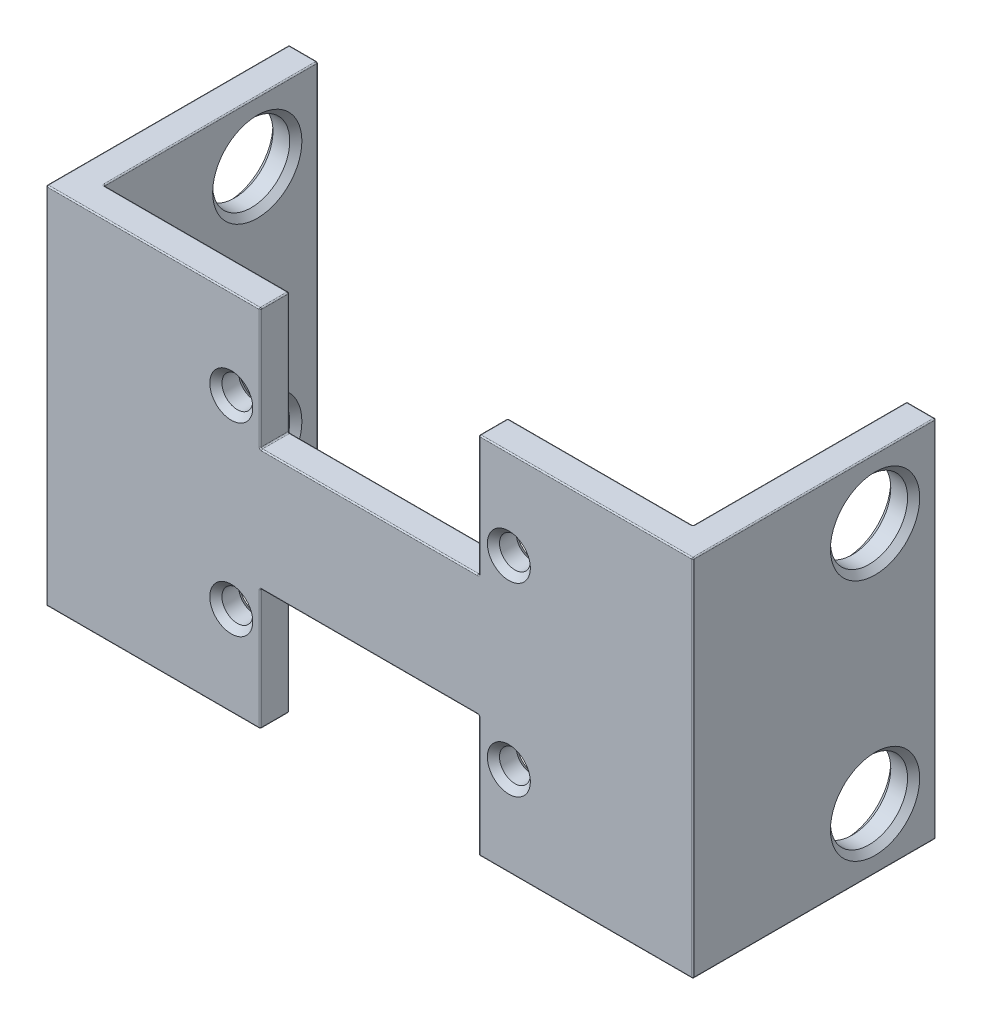
SolidWorks part; units mm, degrees
ref_plane "Front Plane" through (0, 0, 0) normal (0, 0, 1) x (1, 0, 0)
ref_plane "Top Plane" through (0, 0, 0) normal (0, 1, 0) x (1, 0, 0)
ref_plane "Right Plane" through (0, 0, 0) normal (1, 0, 0) x (0, 0, -1)
sketch "Sketch1" plane through (0, 0, 0) normal (0, 1, 0) x (1, 0, 0)
  line L0 (0, 0) -> (0, 17.6188)
  line L1 (0, 17.6188) -> (2.3813, 17.6188)
  line L2 (2.3813, 17.6188) -> (2.3813, -2.3812)
  line L3 (2.3813, -2.3812) -> (-50.8812, -2.3813)
  line L5 (-48.5, 0) -> (0, 0)
  line L6 (-48.5, 0) -> (-48.5, 17.6188)
  line L7 (-48.5, 17.6188) -> (-50.8812, 17.6188)
  line L8 (-50.8812, 17.6188) -> (-50.8812, -2.3813)
  dimension "D1" = 2.3813
  dimension "D2" = 20
  dimension "D4" = 2.3813
  dimension "D5" = 20
  dimension "D6" = 48.5
  dimension "D7" = 2.3813
extrude "Boss-Extrude1" add sketch "Sketch1" along normal blind 30
sketch "Sketch2" plane through (0, 0, 2.3812) normal (0, 0, 1) x (1, 0, 0)
  line L4 (-50.8812, 0) -> (2.3813, 0)
  line L5 (2.3813, 0) -> (2.3813, 30)
  line L6 (2.3813, 30) -> (-50.8812, 30)
  line L7 (-50.8812, 30) -> (-50.8812, 0)
  line L8 (-50.8812, 0) -> (2.3813, 0) construction
  line L9 (2.3813, 0) -> (2.3813, 30) construction
  line L10 (2.3813, 30) -> (-50.8812, 30) construction
  line L12 (-50.8812, 30) -> (-50.8812, 0) construction
  circle A0 centre (-35.64, 7.38) radius 1.27 construction
  circle A1 centre (-35.64, 7.38) radius 1.27
  circle A2 centre (-12.78, 7.38) radius 1.27 construction
  circle A3 centre (-12.78, 7.38) radius 1.27
  circle A4 centre (-12.78, 22.62) radius 1.27 construction
  circle A5 centre (-12.78, 22.62) radius 1.27
  circle A6 centre (-35.64, 22.62) radius 1.27 construction
  circle A7 centre (-35.64, 22.62) radius 1.27
  dimension "D1" = 0
extrude "Cut-Extrude1" cut sketch "Sketch2" against normal through all
sketch "Sketch3" plane through (2.3813, 0, 0) normal (1, 0, 0) x (0, 0, -1)
  line L4 (-2.3812, 0) -> (17.6188, 0)
  line L5 (17.6188, 0) -> (17.6188, 30)
  line L6 (17.6188, 30) -> (-2.3812, 30)
  line L7 (-2.3812, 30) -> (-2.3812, 0)
  line L8 (-2.3812, 0) -> (17.6188, 0) construction
  line L9 (17.6188, 0) -> (17.6188, 30) construction
  line L10 (17.6188, 30) -> (-2.3812, 30) construction
  line L11 (-2.3812, 30) -> (-2.3812, 0) construction
  circle A0 centre (12.6188, 25) radius 3.175
  circle A1 centre (12.6188, 5) radius 3.175
  point P2 (12.6188, 25)
  point P4 (12.6188, 5)
  dimension "D5" = 6.35
  dimension "D2" = 20
  dimension "D3" = 5
  dimension "D4" = 15
  dimension "D1" = 0
extrude "Cut-Extrude2" cut sketch "Sketch3" against normal through all
fillet "Fillet1" radius 0.1 24 edges at (-48.5, 15, -17.6188) (-50.8812, 15, -17.6188) (2.3813, 15, -17.6188) (0, 15, -17.6188) (-48.5, 0, -8.8094) (-49.6906, 0, -17.6188) (-50.8812, 0, -7.6188) (-24.25, 0, 2.3813) (2.3813, 0, -7.6188) (1.1906, 0, -17.6188) (0, 0, -8.8094) (-24.25, 0, 0) (0, 30, -8.8094) (1.1906, 30, -17.6188) (2.3813, 30, -7.6188) (-24.25, 30, 2.3813) (-50.8812, 30, -7.6188) (-49.6906, 30, -17.6188) (-48.5, 30, -8.8094) (-24.25, 30, 0) (-50.8812, 15, 2.3813) (2.3813, 15, 2.3812) (0, 15, 0) (-48.5, 15, 0)
chamfer "Chamfer1" distance 0.5 angle 45 16 edges at (0, 5, -15.7938) (2.3813, 5, -15.7938) (0, 25, -15.7938) (2.3813, 25, -15.7938) (-48.5, 25, -9.4437) (-50.8812, 25, -15.7938) (-48.5, 5, -9.4437) (-50.8812, 5, -15.7938) (-11.51, 7.38, 0) (-11.51, 7.38, 2.3812) (-11.51, 22.62, 0) (-11.51, 22.62, 2.3812) (-34.37, 7.38, 0) (-34.37, 7.38, 2.3812) (-34.37, 22.62, 0) (-34.37, 22.62, 2.3812)
sketch "Sketch4" plane through (0, 0, 2.3812) normal (0, 0, 1) x (1, 0, 0)
  line L0 (-50.7812, 15) -> (-44.8703, 15) construction
  line L4 (2.2813, 29.9) -> (-50.7812, 29.9)
  line L5 (-50.7812, 29.9) -> (-50.7812, 0.1)
  line L6 (-50.7812, 0.1) -> (2.2813, 0.1)
  line L7 (2.2813, 0.1) -> (2.2813, 29.9)
  line L8 (2.2813, 29.9) -> (-50.7812, 29.9) construction
  line L9 (-50.7812, 29.9) -> (-50.7812, 0.1) construction
  line L10 (-50.7812, 0.1) -> (2.2813, 0.1) construction
  line L11 (2.2813, 0.1) -> (2.2813, 29.9) construction
  line L17 (2.2813, 0) -> (-50.7812, 0) construction
  line L18 (2.2813, 0) -> (-50.7812, 0) construction
  line L19 (2.2813, 0) -> (-50.7812, 0) construction
  line L20 (-33.25, 20) -> (-15.25, 20)
  line L21 (-33.25, 0) -> (-15.25, 0)
  line L22 (-33.25, 0) -> (-33.25, 10)
  line L23 (-33.25, 10) -> (-15.25, 10)
  line L24 (-15.25, 0) -> (-15.25, 10)
  line L25 (-15.25, 30) -> (-15.25, 20)
  line L26 (-33.25, 30) -> (-15.25, 30)
  line L27 (-33.25, 30) -> (-33.25, 20)
  point P2 (-24.25, 29.9)
  point P4 (-24.25, 0.1)
  point P6 (-24.25, 10)
  point P12 (-50.7812, 15)
  point P14 (-24.25, 0.1)
  point P15 (0, 0)
  point P22 (0, 0)
  point P23 (-44.8703, 15)
  dimension "D2" = 18
  dimension "D3" = 10
  dimension "D4" = 5.911
  dimension "D1" = 0
extrude "Cut-Extrude4" cut sketch "Sketch4" against normal blind 10
fillet "Fillet2" radius 0.1 28 edges at (-15.25, 0, 1.1906) (-15.25, 0.0293, 0.0293) (-15.25, 5.05, 0) (-15.25, 5.05, 2.3812) (-15.25, 0.0293, 2.352) (-33.25, 5.05, 2.3812) (-33.25, 5.05, 0) (-33.25, 0.0293, 0.0293) (-33.25, 0, 1.1906) (-33.25, 0.0293, 2.352) (-24.25, 10, 0) (-33.25, 10, 1.1906) (-24.25, 10, 2.3812) (-15.25, 10, 1.1906) (-15.25, 24.95, 2.3812) (-15.25, 24.95, 0) (-15.25, 29.9707, 0.0293) (-15.25, 30, 1.1906) (-15.25, 29.9707, 2.352) (-24.25, 20, 0) (-15.25, 20, 1.1906) (-24.25, 20, 2.3812) (-33.25, 30, 1.1906) (-33.25, 29.9707, 0.0293) (-33.25, 24.95, 0) (-33.25, 20, 1.1906) (-33.25, 24.95, 2.3812) (-33.25, 29.9707, 2.352)
